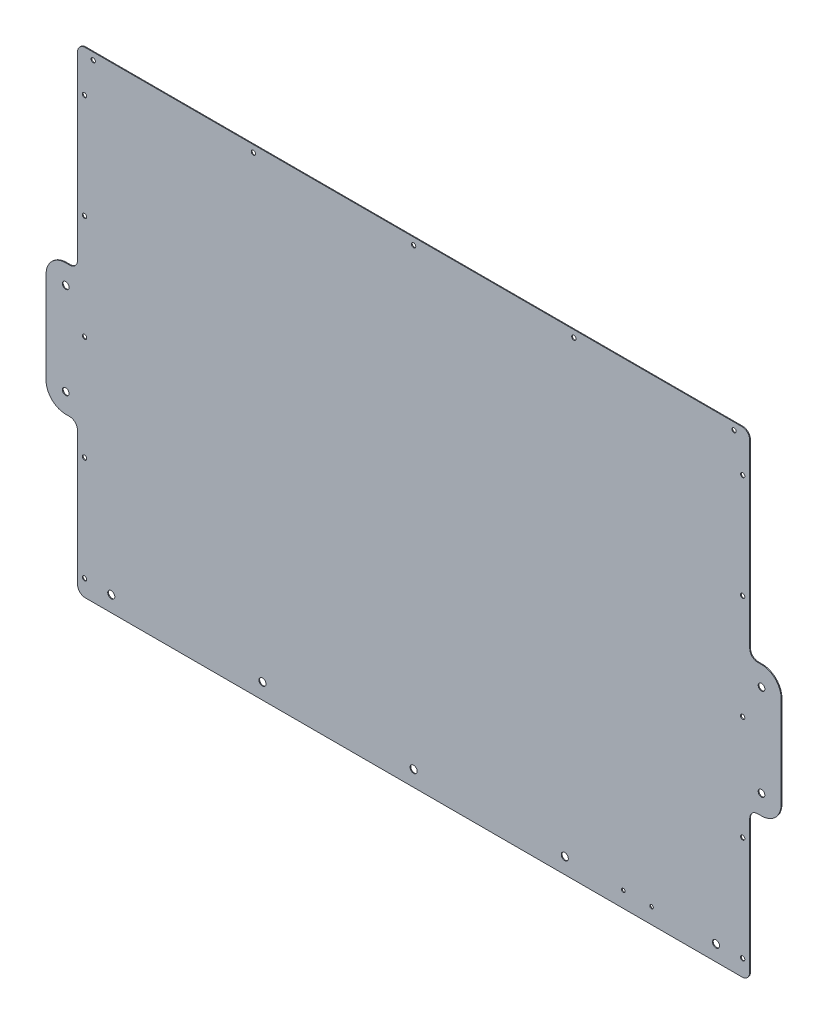
SolidWorks part; units mm, degrees
note: The reader was unsure of these and kept them because the rebuilt part matched: thickness of "Base-Flange1", "Sheet-Metal1", "Sheet-Metal5", "Sheet-Metal6", "Sheet-Metal7", "Sheet-Metal8", "Sheet-Metal9", "Sheet-Metal10".
material "AISI 304"
ref_plane "Front Plane" through (0, 0, 0) normal (0, 0, 1) x (1, 0, 0)
ref_plane "Top Plane" through (0, 0, 0) normal (0, 1, 0) x (1, 0, 0)
ref_plane "Right Plane" through (0, 0, 0) normal (1, 0, 0) x (0, 0, -1)
sketch "Sketch1" plane through (0, 0, 0) normal (0, 0, 1) x (1, 0, 0)
  line L1 (-428, -303.45) -> (428, -303.45)
  line L2 (-428, -303.45) -> (-428, 303.45)
  line L3 (-428, 303.45) -> (428, 303.45)
  line L4 (428, -303.45) -> (428, 303.45)
  line L5 (-428, -303.45) -> (428, 303.45) construction
  line L6 (-428, 303.45) -> (428, -303.45) construction
  point P0 (0, 0)
  dimension "D1" = 856
  dimension "D2" = 606.9
base flange "Base-Flange1" sketch "Sketch1" thickness 1 reverse thickness direction no parameters "D1"=1
ref_plane "Plane3" through (-428, -303.45, 0) normal (0, -1, 0) x (-1, 0, 0)
hole_wizard "M5 Clearance Hole1" positions "Sketch2" profile "Sketch3" hole size "M5" standard "ISO" end condition through all
sketch "Sketch2" plane through (0, 0, -1) normal (0, 0, -1) x (-1, 0, 0)
  point P0 (-419, -282.45)
  point P3 (-419, -149.225)
  point P6 (-419, -16)
  point P9 (-419, 117.225)
  point P12 (-419, 250.45)
  point P15 (-408, 294.45)
  point P18 (-204, 294.45)
  point P21 (0, 294.45)
  point P24 (204, 294.45)
  point P27 (408, 294.45)
  point P30 (419, 250.45)
  point P33 (419, 117.225)
  point P36 (419, -16)
  point P39 (419, -149.225)
  point P42 (419, -282.45)
sketch "Sketch3" plane through (419, -282.45, -1) normal (1, 0, 0) x (0, 1, 0)
  line L0 (0, 0) -> (0, 1)
  line L1 (0, 1) -> (2.75, 1)
  line L2 (2.75, 1) -> (2.75, 0)
  line L5 (2.75, 0) -> (0, 0)
  line L11 (0, -6.35) -> (0, 107.95) construction
  dimension "Thru Hole Dia." = 5.5
  dimension "Thru Hole Depth" = 1
hole_wizard "M8 Clearance Hole1" positions "Sketch4" profile "Sketch5" hole size "M8" standard "ISO" end condition through all
sketch "Sketch4" plane through (0, 0, 0) normal (0, 0, 1) x (1, 0, 0)
  line L0 (-428, -303.45) -> (428, -303.45) construction
  line L1 (-428, 303.45) -> (-428, -303.45) construction
  point P0 (-385, -283.45)
  dimension "D1" = 20
  dimension "D2" = 43
sketch "Sketch5" plane through (-385, -283.45, 0) normal (1, 0, 0) x (0, -1, 0)
  line L0 (0, 0) -> (0, 1)
  line L1 (0, 1) -> (4.5, 1)
  line L2 (4.5, 1) -> (4.5, 0)
  line L5 (4.5, 0) -> (0, 0)
  line L11 (0, -6.35) -> (0, 107.95) construction
  dimension "Thru Hole Dia." = 9
  dimension "Thru Hole Depth" = 1
pattern_linear "LPattern1" count 5 spacing 192.5 along (1, 0, 0) of "M8 Clearance Hole1"
fillet "Fillet1" radius 10 4 edges at (-428, -303.45, -0.5) (428, -303.45, -0.5) (428, 303.45, -0.5) (-428, 303.45, -0.5)
hole_wizard "M4 Clearance Hole1" positions "Sketch6" profile "Sketch7" hole size "M4" standard "ISO" end condition through all
sketch "Sketch6" plane through (0, 0, 0) normal (0, 0, 1) x (1, 0, 0)
  point P0 (267, -283.45)
  point P2 (303, -283.45)
sketch "Sketch7" plane through (267, -283.45, 0) normal (1, 0, 0) x (0, -1, 0)
  line L0 (0, 0) -> (0, 1)
  line L1 (0, 1) -> (2.25, 1)
  line L2 (2.25, 1) -> (2.25, 0)
  line L5 (2.25, 0) -> (0, 0)
  line L11 (0, -6.35) -> (0, 107.95) construction
  dimension "Thru Hole Dia." = 4.5
  dimension "Thru Hole Depth" = 1
sketch "Sketch8" plane through (0, 0, 0) normal (0, 0, 1) x (1, 0, 0)
  line L0 (-428, 293.45) -> (-428, -293.45) construction
  line L1 (-428, 53.55) -> (-443, 53.55)
  line L2 (-428, 53.55) -> (-428, -113.45)
  line L3 (-428, -113.45) -> (-443, -113.45)
  line L4 (-468, 28.55) -> (-468, -88.45)
  line L5 (-418, -303.45) -> (418, -303.45) construction
  line L6 (-443, 28.55) -> (-443, -88.45) construction
  line L7 (-443, -29.95) -> (-468, -29.95) construction
  circle A0 centre (-443, 28.55) radius 4.25
  circle A1 centre (-443, -88.45) radius 4.25
  circle A2 centre (-443, 28.55) radius 14.5 construction
  circle A3 centre (-443, -88.45) radius 14.5 construction
  arc A4 (-468, -88.45) -> (-443, -113.45) centre (-443, -88.45) ccw
  arc A5 (-443, 53.55) -> (-468, 28.55) centre (-443, 28.55) ccw
  dimension "D6" = 29
  dimension "D7" = 8.5
  dimension "D1" = 190
  dimension "D2" = 117
  dimension "D3" = 25
  dimension "D4" = 15
  dimension "D5" = 167
extrude "Boss-Extrude1" add sketch "Sketch8" against normal blind 1
mirror "Mirror3" about plane through (0, 0, 0) normal (1, 0, 0) of "Boss-Extrude1"
fillet "Fillet2" radius 10 4 edges at (-428, -113.45, -0.5) (-428, 53.55, -0.5) (428, -113.45, -0.5) (428, 53.55, -0.5)
sketch "Bend-Lines1" [suppressed] plane through (0, 0, 0) normal (0, 1, 0) x (1, 0, 0)
sketch "Bounding-Box1" [suppressed] plane through (0, 0, 0) normal (0, 1, 0) x (1, 0, 0)
sheet metal parameters "Sheet-Metal1" thickness 1 parameters "D1"=1, "D7"=1.5
flat pattern "Flat-Pattern1" [suppressed]
sketch "Bend-Lines2" plane through (0, 0, 0) normal (0, 0, 1) x (1, 0, 0)
sketch3d "Bounding-Box2" [suppressed]
  line L0 (-424, -292.2, 0) -> (424, -292.2, 0) construction
  line L1 (-424, 292.2, 0) -> (424, 292.2, 0) construction
  line L2 (-424, -292.2, 0) -> (-424, 292.2, 0) construction
  line L3 (424, -292.2, 0) -> (424, 292.2, 0) construction
sheet metal parameters "Sheet-Metal5" thickness 1 parameters "D1"=1, "D7"=1.5
flat pattern "Flat-Pattern1"
sketch "Bend-Lines2" plane through (0, 0, 0) normal (0, 0, 1) x (1, 0, 0)
sketch3d "Bounding-Box2" [suppressed]
  line L0 (-448, -303.45, 0) -> (448, -303.45, 0) construction
  line L1 (-448, 303.45, 0) -> (448, 303.45, 0) construction
  line L2 (-448, -303.45, 0) -> (-448, 303.45, 0) construction
  line L3 (448, -303.45, 0) -> (448, 303.45, 0) construction
sheet metal parameters "Sheet-Metal6" thickness 1 parameters "D1"=1, "D7"=1.5
flat pattern "Flat-Pattern1"
sketch "Bend-Lines2" plane through (0, 0, 0) normal (0, 0, 1) x (1, 0, 0)
sketch3d "Bounding-Box2" [suppressed]
  line L0 (-448, -303.45, 0) -> (448, -303.45, 0) construction
  line L1 (-448, 303.45, 0) -> (448, 303.45, 0) construction
  line L2 (-448, -303.45, 0) -> (-448, 303.45, 0) construction
  line L3 (448, -303.45, 0) -> (448, 303.45, 0) construction
sheet metal parameters "Sheet-Metal7" thickness 1 parameters "D1"=1, "D7"=1.5
flat pattern "Flat-Pattern1"
sketch "Bend-Lines2" plane through (0, 0, 0) normal (0, 0, 1) x (1, 0, 0)
sketch3d "Bounding-Box2" [suppressed]
  line L0 (-428, 303.45, 0) -> (428, 303.45, 0) construction
  line L1 (-428, -303.45, 0) -> (428, -303.45, 0) construction
  line L2 (-428, 303.45, 0) -> (-428, -303.45, 0) construction
  line L3 (428, 303.45, 0) -> (428, -303.45, 0) construction
sheet metal parameters "Sheet-Metal8" thickness 1 parameters "D1"=1, "D7"=1.5
flat pattern "Flat-Pattern1"
sketch "Bend-Lines2" plane through (0, 0, 0) normal (0, 0, 1) x (1, 0, 0)
sketch3d "Bounding-Box2" [suppressed]
  line L0 (-428, 303.45, 0) -> (428, 303.45, 0) construction
  line L1 (-428, -303.45, 0) -> (428, -303.45, 0) construction
  line L2 (-428, 303.45, 0) -> (-428, -303.45, 0) construction
  line L3 (428, 303.45, 0) -> (428, -303.45, 0) construction
sheet metal parameters "Sheet-Metal9" thickness 1 parameters "D1"=1, "D7"=1.5
flat pattern "Flat-Pattern1"
sketch "Bend-Lines2" plane through (0, 0, 0) normal (0, 0, 1) x (1, 0, 0)
sketch3d "Bounding-Box2" [suppressed]
  line L0 (-478, 303.45, 0) -> (428, 303.45, 0) construction
  line L1 (-478, -303.45, 0) -> (428, -303.45, 0) construction
  line L2 (-478, 303.45, 0) -> (-478, -303.45, 0) construction
  line L3 (428, 303.45, 0) -> (428, -303.45, 0) construction
sheet metal parameters "Sheet-Metal10" thickness 1 parameters "D1"=1, "D7"=1.5
flat pattern "Flat-Pattern1"
sketch "Bend-Lines2" plane through (0, 0, 0) normal (0, 0, 1) x (1, 0, 0)
sketch3d "Bounding-Box2" [suppressed]
  line L0 (-468, 303.45, 0) -> (468, 303.45, 0) construction
  line L1 (-468, -303.45, 0) -> (468, -303.45, 0) construction
  line L2 (-468, 303.45, 0) -> (-468, -303.45, 0) construction
  line L3 (468, 303.45, 0) -> (468, -303.45, 0) construction
